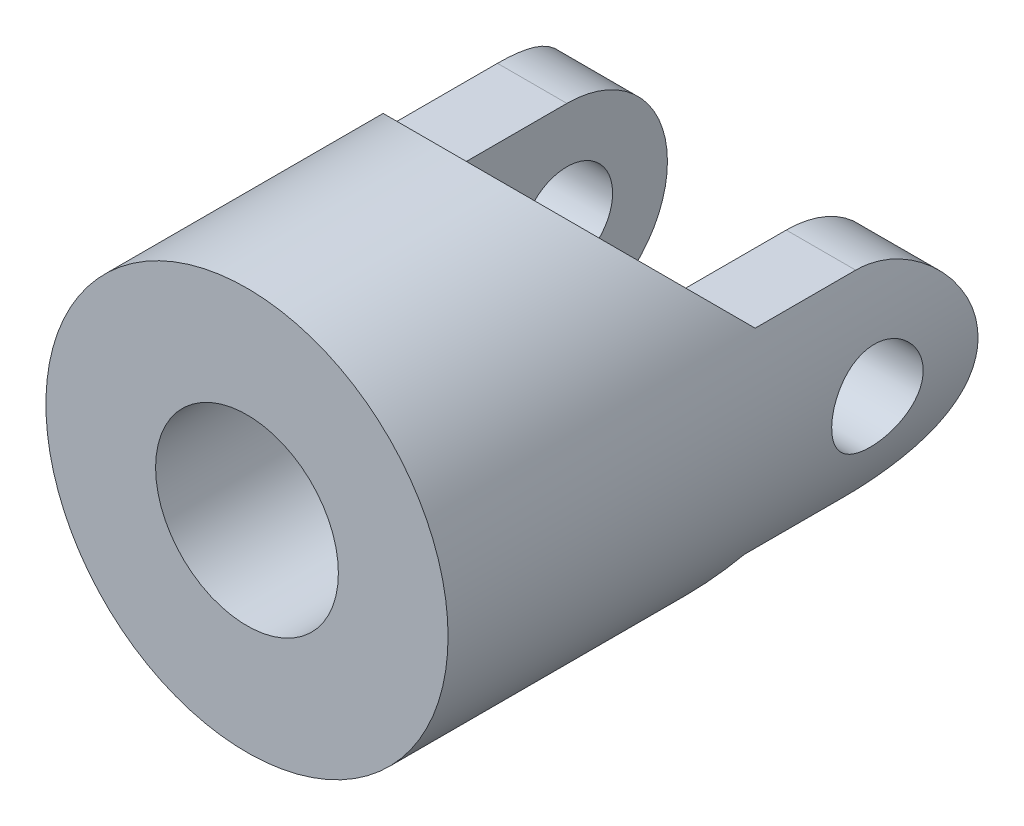
SolidWorks part; units mm, degrees
ref_plane "前视基准面" through (0, 0, 0) normal (0, 0, 1) x (1, 0, 0)
ref_plane "上视基准面" through (0, 0, 0) normal (0, 1, 0) x (1, 0, 0)
ref_plane "右视基准面" through (0, 0, 0) normal (1, 0, 0) x (0, 0, -1)
sketch "草图1" plane through (0, 0, 0) normal (0, 0, 1) x (1, 0, 0)
  circle A1 centre (0, 0) radius 11
  dimension "D1" = 22
extrude "凸台-拉伸1" add sketch "草图1" along normal blind 29
sketch "草图2" plane through (0, 0, 0) normal (1, 0, 0) x (0, 0, -1)
  line L0 (-17, 11) -> (-11, 5)
  line L1 (0, 11) -> (-29, 11) construction
  line L2 (-11, 5) -> (0, 5)
  line L3 (0, -11) -> (0, 11) construction
  line L4 (0, 5) -> (0, -6)
  line L5 (0, -6) -> (-11, -6)
  line L6 (-11, -6) -> (-17, -12)
  line L7 (-17, -12) -> (0, -12)
  line L8 (0, -12) -> (0, -6)
  line L9 (0, 5) -> (0, 11)
  line L10 (0, 11) -> (-17, 11)
  line L11 (-29, 11) -> (-29, -11) construction
  dimension "D1" = 11
  dimension "D2" = 6
  dimension "D3" = 6
  dimension "D4" = 12
  dimension "D5" = 12
  dimension "D6" = 135
  dimension "D7" = 135
extrude "切除-拉伸1" cut sketch "草图2" against normal blind 29 and the other way blind 29 contours L9 L10 L0 L2 | L7 L8 L5 L6 region at (0, 8.2143, 7.1071) region at (0, -9.2143, 7.1071)
sketch "草图3" plane through (0, 0, 0) normal (0, 0, -1) x (-1, 0, 0)
  line L1 (-6, 11.9789) -> (6, 11.9789)
  line L2 (-6, 11.9789) -> (-6, -11.9789)
  line L3 (-6, -11.9789) -> (6, -11.9789)
  line L4 (6, 11.9789) -> (6, -11.9789)
  line L5 (-6, 11.9789) -> (6, -11.9789) construction
  line L6 (-6, -11.9789) -> (6, 11.9789) construction
  point P0 (0, 0)
  dimension "D1" = 12
extrude "切除-拉伸2" cut sketch "草图3" against normal blind 14
fillet "圆角1" radius 5.5 4 edges at (-7.899, 5, 0) (-7.6098, -6, 0) (7.6098, -6, 0) (7.899, 5, 0)
sketch "草图4" plane through (0, 0, 29) normal (0, 0, 1) x (1, 0, 0)
  circle A0 centre (0, 0) radius 5
  dimension "D1" = 10
extrude "切除-拉伸3" cut sketch "草图4" against normal blind 17
sketch "草图5" plane through (-6, 0, 0) normal (1, 0, 0) x (0, 0, -1)
  circle A0 centre (-5.5, -0.5) radius 2.5
  dimension "D1" = 5
extrude "切除-拉伸4" cut sketch "草图5" against normal blind 17 and the other way blind 17
